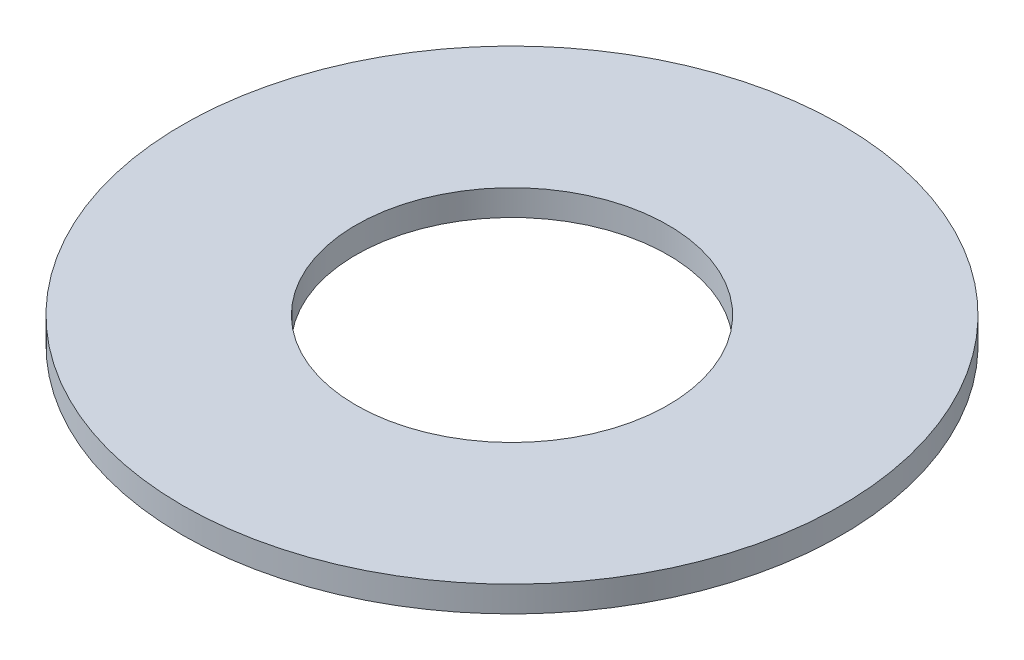
SolidWorks part; units mm, degrees
material "Alum Plate"
ref_plane "Front Plane" through (0, 0, 0) normal (0, 0, 1) x (1, 0, 0)
ref_plane "Top Plane" through (0, 0, 0) normal (0, 1, 0) x (1, 0, 0)
ref_plane "Right Plane" through (0, 0, 0) normal (1, 0, 0) x (0, 0, -1)
other "Bounding Box"
ref_plane "Default Plane" through (0, 2.286, 19.05) normal (0, -1, 0) x (-1, 0, 0)
sketch "Sketch1" plane through (0, 0, 0) normal (0, 1, 0) x (1, 0, 0)
  circle A0 centre (0, 0) radius 4.7625
  circle A1 centre (0, 0) radius 10.0584
  dimension "D1" = 9.525
  dimension "D2" = 20.1168
extrude "Boss-Extrude1" add sketch "Sketch1" along normal blind 0.7874
equation "\"Unit Measure\"= \"BoundingVolume\" / \"Thickness\"'in^2"
